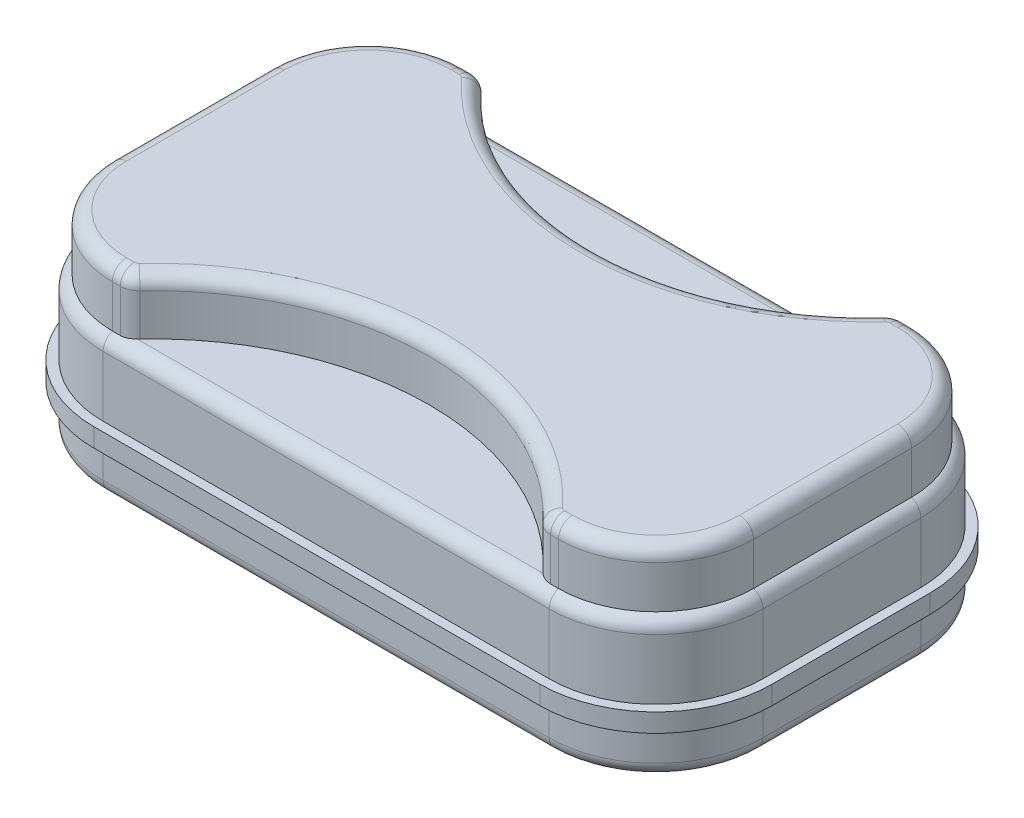
SolidWorks part; units mm, degrees
ref_plane "Front Plane" through (0, 0, 0) normal (0, 0, 1) x (1, 0, 0)
ref_plane "Top Plane" through (0, 0, 0) normal (0, 1, 0) x (1, 0, 0)
ref_plane "Right Plane" through (0, 0, 0) normal (1, 0, 0) x (0, 0, -1)
sketch "Sketch1" plane through (0, 0, 0) normal (0, 1, 0) x (1, 0, 0)
  line L0 (-23.5, 21) -> (-24.5, 21)
  line L1 (-23.5, 21) -> (23.5, 21)
  line L3 (-23.5, -21) -> (23.5, -21)
  line L4 (36, 8.5) -> (36, -8.5)
  line L5 (-36, 21) -> (36, -21) construction
  line L6 (-36, -21) -> (36, 21) construction
  line L7 (-37, 8.5) -> (-37, -8.5)
  line L8 (-24.5, -21) -> (-23.5, -21)
  arc A1 (23.5, -21) -> (36, -8.5) centre (23.5, -8.5) ccw
  arc A2 (23.5, 21) -> (36, 8.5) centre (23.5, 8.5) cw
  arc A4 (-37, -8.5) -> (-24.5, -21) centre (-24.5, -8.5) ccw
  arc A5 (-24.5, 21) -> (-37, 8.5) centre (-24.5, 8.5) ccw
  point P0 (0, 0)
  dimension "D5" = 12.5
  dimension "D1" = 72
  dimension "D2" = 42
extrude "Boss-Extrude1" add sketch "Sketch1" along normal blind 2
sketch "Sketch2" plane through (0, 0, 0) normal (0, -1, 0) x (1, 0, 0)
  line L4 (-36, 8.5) -> (-36, -8.5)
  line L5 (-36, 8.5) -> (-36, -8.5)
  line L9 (-24.5, -20) -> (23.5, -20)
  line L10 (35, -8.5) -> (35, 8.5)
  line L11 (23.5, 20) -> (-24.5, 20)
  line L13 (-24.5, -20) -> (23.5, -20)
  line L14 (35, -8.5) -> (35, 8.5)
  line L15 (23.5, 20) -> (-24.5, 20)
  arc A4 (-24.5, 20) -> (-36, 8.5) centre (-24.5, 8.5) ccw
  arc A5 (-24.5, 20) -> (-36, 8.5) centre (-24.5, 8.5) ccw
  arc A6 (-36, -8.5) -> (-24.5, -20) centre (-24.5, -8.5) ccw
  arc A7 (-36, -8.5) -> (-24.5, -20) centre (-24.5, -8.5) ccw
  arc A10 (23.5, -20) -> (35, -8.5) centre (23.5, -8.5) ccw
  arc A11 (35, 8.5) -> (23.5, 20) centre (23.5, 8.5) ccw
  arc A14 (23.5, -20) -> (35, -8.5) centre (23.5, -8.5) ccw
  arc A15 (35, 8.5) -> (23.5, 20) centre (23.5, 8.5) ccw
  dimension "D1" = 1
extrude "Boss-Extrude2" add sketch "Sketch2" along normal blind 5
sketch "Sketch3" plane through (0, 2, 0) normal (0, 1, 0) x (1, 0, 0)
  line L4 (-36, 8.5) -> (-36, -8.5)
  line L5 (-36, 8.5) -> (-36, -8.5)
  line L8 (-24.5, -20) -> (23.5, -20)
  line L9 (35, -8.5) -> (35, 8.5)
  line L10 (23.5, 20) -> (-24.5, 20)
  line L12 (-24.5, -20) -> (23.5, -20)
  line L13 (35, -8.5) -> (35, 8.5)
  line L14 (23.5, 20) -> (-24.5, 20)
  arc A4 (-24.5, 20) -> (-36, 8.5) centre (-24.5, 8.5) ccw
  arc A5 (-24.5, 20) -> (-36, 8.5) centre (-24.5, 8.5) ccw
  arc A6 (-36, -8.5) -> (-24.5, -20) centre (-24.5, -8.5) ccw
  arc A7 (-36, -8.5) -> (-24.5, -20) centre (-24.5, -8.5) ccw
  arc A9 (23.5, -20) -> (35, -8.5) centre (23.5, -8.5) ccw
  arc A10 (35, 8.5) -> (23.5, 20) centre (23.5, 8.5) ccw
  arc A13 (23.5, -20) -> (35, -8.5) centre (23.5, -8.5) ccw
  arc A14 (35, 8.5) -> (23.5, 20) centre (23.5, 8.5) ccw
  dimension "D1" = 1
extrude "Boss-Extrude3" add sketch "Sketch3" along normal blind 8
sketch "Sketch4" plane through (0, 10, 0) normal (0, 1, 0) x (1, 0, 0)
  line L18 (-0.5, 19) -> (-0.5, 8.9144) construction
  line L19 (0, 0) -> (11.1861, 0) construction
  line L20 (-22.7645, 19) -> (-24.5, 19)
  line L21 (21.7645, -19) -> (23.5, -19)
  line L22 (23.5, 19) -> (-24.5, 19)
  line L23 (34, -8.5) -> (34, 8.5)
  line L24 (-24.5, -19) -> (23.5, -19)
  line L25 (-35, 8.5) -> (-35, -8.5)
  line L26 (23.5, 19) -> (21.7645, 19)
  line L27 (34, -8.5) -> (34, 8.5)
  line L28 (-24.5, -19) -> (-22.7645, -19)
  line L29 (-35, 8.5) -> (-35, -8.5)
  arc A21 (-22.7645, 19) -> (21.7645, 19) centre (-0.5, 38.5323) ccw
  arc A22 (-22.7645, -19) -> (21.7645, -19) centre (-0.5, -38.5323) cw
  arc A25 (34, 8.5) -> (23.5, 19) centre (23.5, 8.5) ccw
  arc A26 (23.5, -19) -> (34, -8.5) centre (23.5, -8.5) ccw
  arc A27 (-35, -8.5) -> (-24.5, -19) centre (-24.5, -8.5) ccw
  arc A28 (-24.5, 19) -> (-35, 8.5) centre (-24.5, 8.5) ccw
  arc A29 (34, 8.5) -> (23.5, 19) centre (23.5, 8.5) ccw
  arc A30 (23.5, -19) -> (34, -8.5) centre (23.5, -8.5) ccw
  arc A31 (-35, -8.5) -> (-24.5, -19) centre (-24.5, -8.5) ccw
  arc A32 (-24.5, 19) -> (-35, 8.5) centre (-24.5, 8.5) ccw
  dimension "D1" = 1
extrude "Boss-Extrude4" add sketch "Sketch4" along normal blind 6
fillet "Fillet1" radius 2 4 edges at (21.7645, 13, 19) (21.7645, 13, -19) (-22.7645, 13, -19) (-22.7645, 13, 19)
fillet "Fillet2" radius 1.5 26 edges at (-0.5, -5, 20) (31.6317, -5, 16.6317) (35, -5, 0) (31.6317, -5, -16.6317) (-0.5, -5, -20) (-0.5, 10, -20) (-0.5, 10, 20) (23.0764, 16, -19) (30.9246, 16, -15.9246) (34, 16, 0) (30.9246, 16, 15.9246) (23.0764, 16, 19) (-0.5, 16, 8.9144) (-24.0764, 16, 19) (-31.9246, 16, 15.9246) (-35, 16, 0) (-31.9246, 16, -15.9246) (-24.0764, 16, -19) (-0.5, 16, -8.9144) (-32.6317, -5, -16.6317) (-36, -5, 0) (-32.6317, -5, 16.6317) (21.854, 16, -18.8336) (21.854, 16, 18.8336) (-22.854, 16, 18.8336) (-22.854, 16, -18.8336)
